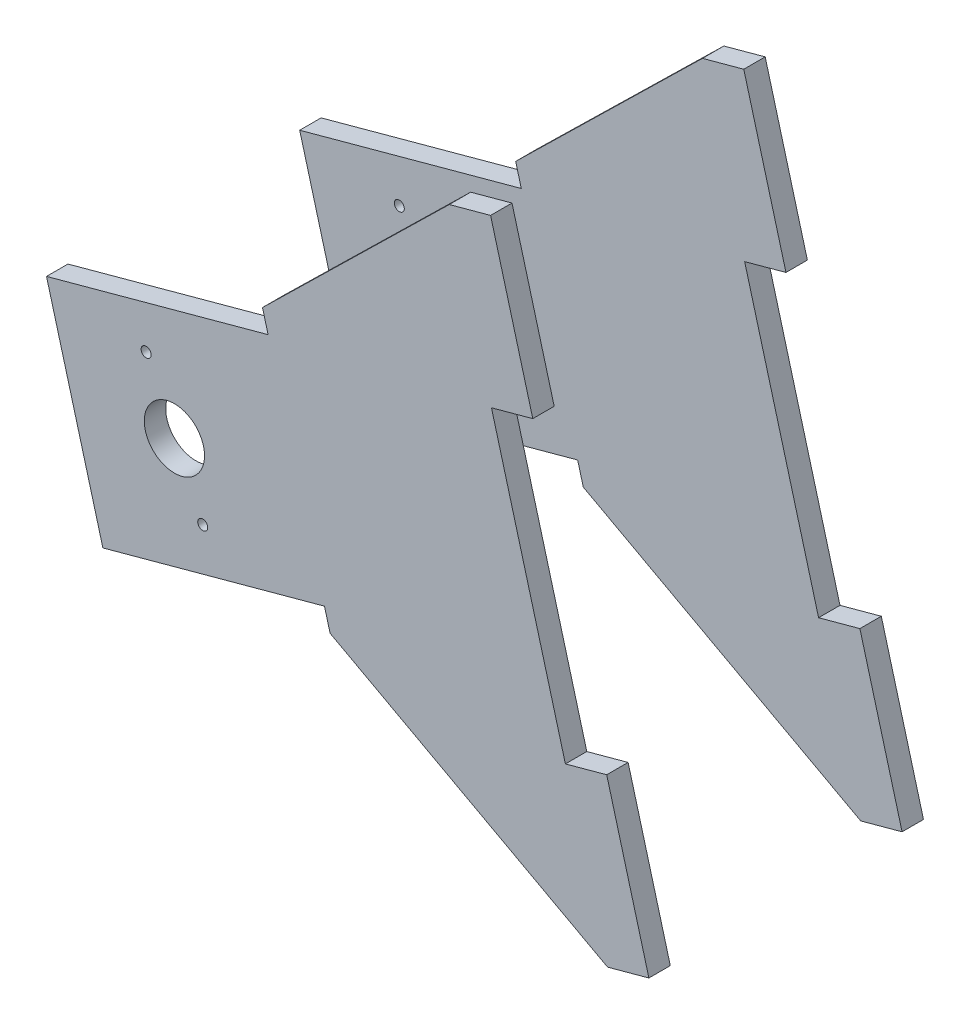
SolidWorks part; units mm, degrees
material "Gillfab4009"
ref_plane "Front Plane" through (0, 0, 0) normal (0, 0, 1) x (1, 0, 0)
ref_plane "Top Plane" through (0, 0, 0) normal (0, 1, 0) x (1, 0, 0)
ref_plane "Right Plane" through (0, 0, 0) normal (1, 0, 0) x (0, 0, -1)
sketch "Sketch1" plane through (2328.5898, 466.462, -4.004) normal (0, 0, 1) x (0.9649, 0.2628, 0)
  line L1 (-2161.2189, 236.8927) -> (-2270.2189, 236.8927)
  line L2 (-2270.2189, 236.8927) -> (-2270.2189, 135.0855)
  line L3 (-2270.2189, 135.0855) -> (-2161.2189, 135.0855)
  line L5 (-2052.9116, 85.557) -> (-2052.9116, 9.357) construction
  line L6 (-2161.2189, 236.8927) -> (-2161.2189, 135.0855) construction
  line L7 (-2222.2031, 135.0855) -> (-2220.1272, 236.8927) construction
  line L8 (-2052.9116, 231.1773) -> (-2052.9116, 97.657)
  line L9 (-2161.2189, 135.0855) -> (-2161.2189, 124.9255)
  line L10 (-2161.2189, 124.9255) -> (-2052.9116, 21.457)
  line L11 (-2161.2189, 236.8927) -> (-2161.2189, 247.0527)
  line L12 (-2161.2189, 247.0527) -> (-2052.9116, 307.3773)
  line L13 (-2052.9116, 307.3773) -> (-2032.5916, 307.3773)
  line L14 (-2032.5916, 307.3773) -> (-2032.5916, 231.1773)
  line L15 (-2032.5916, 231.1773) -> (-2052.9116, 231.1773)
  line L16 (-2052.9116, 21.457) -> (-2032.5916, 21.457)
  line L17 (-2032.5916, 21.457) -> (-2032.5916, 97.657)
  line L18 (-2032.5916, 97.657) -> (-2052.9116, 97.657)
  line L19 (-2052.9116, 97.657) -> (-2052.9116, 21.457) construction
  circle A0 centre (-2221.1651, 185.9891) radius 9.5377 construction
  circle A1 centre (-2221.1651, 185.9891) radius 9.5377 construction
  circle A2 centre (-2352.5682, 163.2853) radius 151.5212 construction
  circle A3 centre (-2221.1651, 185.9891) radius 14.2875
  circle A4 centre (-2226.5708, 217.2755) radius 2.3813 construction
  circle A5 centre (-2215.7595, 154.7026) radius 2.3812 construction
  circle A6 centre (-2226.5708, 217.2755) radius 2.3813
  circle A7 centre (-2215.7595, 154.7026) radius 2.3812
  point P17 (-2221.1651, 185.9891)
  dimension "D1" = 28.575
  dimension "D2" = 113.6285
  dimension "D3" = 108.3073
  dimension "D4" = 10.16
  dimension "D5" = 215.4357
  dimension "D6" = 10.16
  dimension "D7" = 285.9203
  dimension "D8" = 109
  dimension "D9" = 76.2
  dimension "D10" = 20.32
  dimension "D11" = 76.2
extrude "Boss-Extrude1" add sketch "Sketch1" along normal blind 10.16 from offset 90 offset against normal yes
extrude "Boss-Extrude2" add sketch "Sketch1<2>" along normal blind 10.16 from offset 210.16 separate body offset against normal yes
sketch "Sketch1<2>" plane through (2328.5898, 466.462, -4.004) normal (0, 0, 1) x (0.9649, 0.2628, 0) same geometry as "Sketch1"
